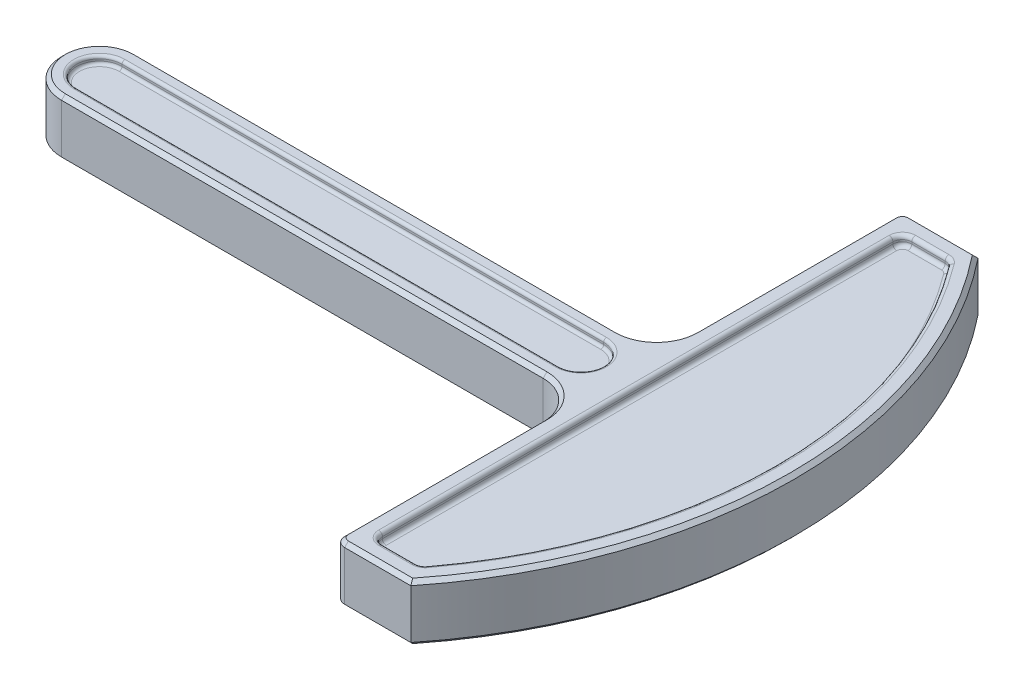
SolidWorks part; units mm, degrees
ref_plane "Front Plane" through (0, 0, 0) normal (0, 0, 1) x (1, 0, 0)
ref_plane "Top Plane" through (0, 0, 0) normal (0, 1, 0) x (1, 0, 0)
ref_plane "Right Plane" through (0, 0, 0) normal (1, 0, 0) x (0, 0, -1)
sketch "Sketch1" plane through (0, 0, 0) normal (0, 1, 0) x (1, 0, 0)
  line L0 (0, 0) -> (-50000, 0) construction
  line L1 (147.3499, 10) -> (0, 10)
  line L2 (147.3499, 75) -> (147.3499, -75)
  line L3 (147.3499, -10) -> (0, -10)
  line L4 (0, 10) -> (0, -10)
  line L5 (147.3499, 10) -> (0, -10) construction
  line L6 (147.3499, -10) -> (0, 10) construction
  line L7 (167.3499, 75) -> (147.3499, 75)
  line L8 (167.3499, -75) -> (147.3499, -75)
  arc A0 (167.3499, 75) -> (167.3499, -75) centre (73.675, 0) cw
  point P0 (73.675, 0)
  point P5 (0, 0)
  dimension "D4" = 120
  dimension "D1" = 20
  dimension "D2" = 150
  dimension "D3" = 20
extrude "Boss-Extrude1" add sketch "Sketch1" along normal mid plane 15 contours A0 L7 L2 L8 | L1 L4 L3 L2 region at (73.675, 0, 0) region at (167.1177, 0, 0)
fillet "Fillet1" radius 10 2 edges at (147.3499, 0, -10) (147.3499, 0, 10)
fillet "Fillet2" 2 edges at (0, 0, 10) (0, 0, -10) type full round first side face at (68.675, 0, 10) second side face at (68.675, 0, -10) middle face at (0, 0, 0)
fillet "Fillet3" radius 2.5 2 edges at (147.3499, 0, -75) (147.3499, 0, 75)
chamfer "Chamfer1" distance 1 angle 45 22 edges at (158.5999, 7.5, -75) (148.0822, 7.5, -74.2678) (147.3499, 7.5, -46.25) (144.421, 7.5, -12.9289) (73.675, 7.5, -10) (0, 7.5, 0) (73.675, 7.5, 10) (158.5999, 7.5, 75) (144.421, 7.5, 12.9289) (148.0822, 7.5, 74.2678) (147.3499, 7.5, 46.25) (158.5999, -7.5, -75) (148.0822, -7.5, -74.2678) (158.5999, -7.5, 75) (147.3499, -7.5, -46.25) (148.0822, -7.5, 74.2678) (144.421, -7.5, -12.9289) (147.3499, -7.5, 46.25) (73.675, -7.5, -10) (144.421, -7.5, 12.9289) (0, -7.5, 0) (73.675, -7.5, 10)
chamfer "Chamfer2" distance 1 angle 45 2 edges at (193.675, -7.5, 0) (193.675, 7.5, 0)
sketch "Sketch2" plane through (0, 7.5, 0) normal (0, 1, 0) x (1, 0, 0)
  line L0 (147.3499, -72.5) -> (147.3499, -20) construction
  line L1 (167.3499, -75) -> (149.8499, -75) construction
  line L2 (149.8499, 75) -> (167.3499, 75) construction
  line L3 (147.3499, 20) -> (147.3499, 72.5) construction
  line L4 (147.3499, -72.5) -> (147.3499, -20)
  line L5 (167.3499, -75) -> (149.8499, -75)
  line L6 (149.8499, 75) -> (167.3499, 75)
  line L7 (147.3499, 20) -> (147.3499, 72.5)
  line L8 (152.3499, -20) -> (152.3499, 70)
  line L9 (152.3499, 70) -> (164.9164, 70)
  line L10 (164.9164, -70) -> (152.3499, -70)
  line L11 (152.3499, -70) -> (152.3499, -20)
  line L12 (152.3499, 20) -> (152.3499, 70) construction
  arc A0 (147.3499, -72.5) -> (149.8499, -75) centre (149.8499, -72.5) ccw construction
  arc A1 (167.3499, -75) -> (167.3499, 75) centre (73.675, 0) ccw construction
  arc A2 (149.8499, 75) -> (147.3499, 72.5) centre (149.8499, 72.5) ccw construction
  arc A3 (147.3499, -72.5) -> (149.8499, -75) centre (149.8499, -72.5) ccw
  arc A4 (167.3499, -75) -> (167.3499, 75) centre (73.675, 0) ccw
  arc A5 (149.8499, 75) -> (147.3499, 72.5) centre (149.8499, 72.5) ccw
  arc A6 (152.3499, 70) -> (152.3499, 70) centre (152.3499, 70) ccw
  arc A7 (164.9164, -70) -> (164.9164, 70) centre (73.675, 0) ccw
  arc A8 (152.3499, -70) -> (152.3499, -70) centre (152.3499, -70) ccw
  dimension "D1" = 5
extrude "Cut-Extrude1" cut sketch "Sketch2" against normal blind 2.5 contours L10 A7 L9 L8 L11 region at (167.5735, 7.5, 0)
mirror "Mirror1" about plane through (0, 0, 0) normal (0, 1, 0) of "Cut-Extrude1"
fillet "Fillet4" radius 2.5 8 edges at (164.9164, 6.25, 70) (152.3499, 6.25, 70) (164.9164, 6.25, -70) (152.3499, 6.25, -70) (164.9164, -6.25, -70) (152.3499, -6.25, -70) (164.9164, -6.25, 70) (152.3499, -6.25, 70)
fillet "Fillet5" radius 1 32 edges at (153.0822, 7.5, -69.2678) (152.3499, 7.5, 0) (153.0822, 7.5, 69.2678) (159.2625, 7.5, 70) (164.793, 7.5, 69.7361) (188.675, 7.5, 0) (164.793, 7.5, -69.7361) (153.0822, 5, -69.2678) (152.3499, 5, 0) (153.0822, 5, 69.2678) (159.2625, 5, 70) (164.793, 5, 69.7361) (188.675, 5, 0) (164.793, 5, -69.7361) (159.2625, 7.5, -70) (159.2625, 5, -70) (153.0822, -7.5, -69.2678) (152.3499, -7.5, 0) (153.0822, -7.5, 69.2678) (159.2625, -7.5, 70) (164.793, -7.5, 69.7361) (188.675, -7.5, 0) (164.793, -7.5, -69.7361) (153.0822, -5, -69.2678) (152.3499, -5, 0) (153.0822, -5, 69.2678) (159.2625, -5, 70) (164.793, -5, 69.7361) (188.675, -5, 0) (164.793, -5, -69.7361) (159.2625, -7.5, -70) (159.2625, -5, -70)
sketch "Sketch3" plane through (0, 7.5, 0) normal (0, 1, 0) x (1, 0, 0)
  line L0 (10, 0) -> (137.3499, 0) construction
  line L1 (10, 6) -> (137.3499, 6)
  line L2 (10, -6) -> (137.3499, -6)
  arc A0 (10, 6) -> (10, -6) centre (10, 0) ccw
  arc A1 (137.3499, -6) -> (137.3499, 6) centre (137.3499, 0) ccw
  arc A2 (10, 9) -> (10, -9) centre (10, 0) ccw construction
  point P4 (73.675, 0)
  dimension "D1" = 6
extrude "Cut-Extrude2" cut sketch "Sketch3" against normal blind 2
mirror "Mirror2" about plane through (0, 0, 0) normal (0, 1, 0) of "Cut-Extrude2"
fillet "Fillet6" radius 0.75 16 edges at (73.675, -5.5, -6) (143.3499, -5.5, 0) (73.675, -5.5, 6) (73.675, -7.5, -6) (143.3499, -7.5, 0) (73.675, -7.5, 6) (73.675, 5.5, -6) (143.3499, 5.5, 0) (73.675, 5.5, 6) (73.675, 7.5, -6) (143.3499, 7.5, 0) (73.675, 7.5, 6) (4, -5.5, 0) (4, -7.5, 0) (4, 5.5, 0) (4, 7.5, 0)
